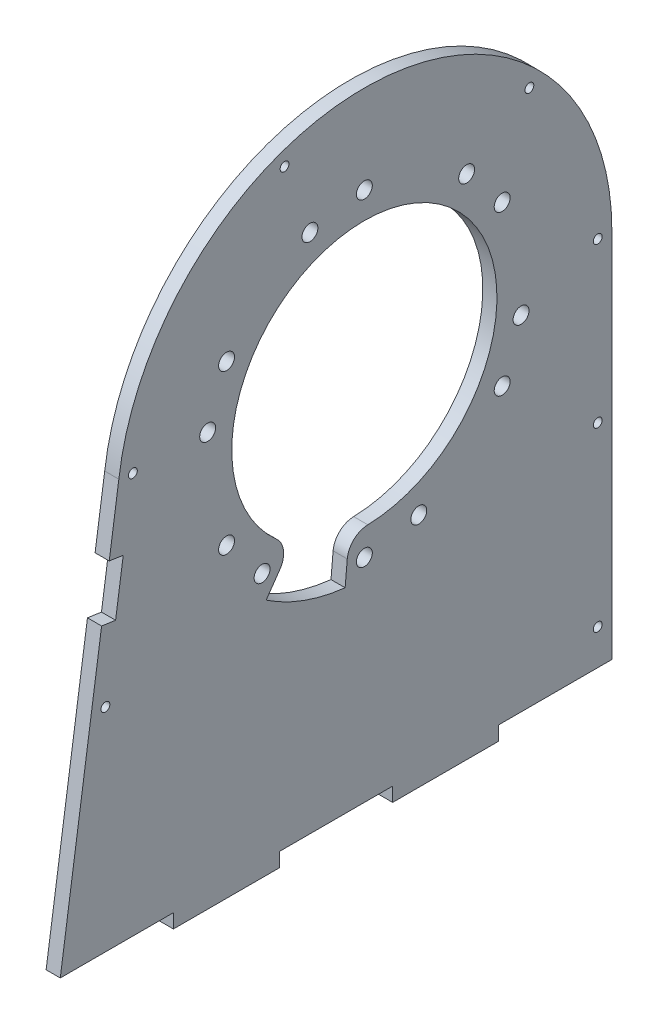
SolidWorks part; units mm, degrees
ref_plane "Ebene vorne" through (0, 0, 0) normal (1, 0, 0) x (0, 1, 0)
ref_plane "Ebene oben" through (0, 0, 0) normal (0, 0, 1) x (0, 1, 0)
ref_plane "Ebene rechts" through (0, 0, 0) normal (0, 1, 0) x (-1, 0, 0)
sketch "Skizze1" plane through (0, 0, 0) normal (1, 0, 0) x (0, 0, -1)
  line L0 (-80.9035, -101.1719) -> (-80.9035, -97.0207)
  line L1 (-121.1235, -18.7355) -> (-120.9035, -18.7355) construction
  line L2 (-96.4035, -81.5207) -> (-102.1906, -81.5207)
  line L3 (-80.9035, -63.7029) -> (-80.9035, -66.0207)
  line L4 (-80.9035, -101.1719) -> (-80.9035, -97.0207)
  line L5 (-61.4088, -81.5207) -> (-65.4035, -81.5207)
  line L6 (-80.9035, -66.0207) -> (-80.9035, -63.7029)
  line L7 (-120.9035, -13.3959) -> (-120.9035, -24.0751)
  line L39 (-10.9035, -186.5207) -> (-166.9035, -186.5207)
  line L40 (-166.9035, -186.5207) -> (-150.3378, -72.6399)
  line L41 (-61.4088, -81.5207) -> (-65.4035, -81.5207)
  line L42 (-10.9035, -81.5207) -> (-10.9035, -186.5207)
  line L43 (-166.9035, -186.5207) -> (-121.9035, -186.5207)
  line L47 (-10.9035, -186.5207) -> (-81.9035, -186.5207)
  line L52 (-1.9035, -186.5207) -> (-10.9035, -186.5207)
  line L54 (-1.9035, -81.5207) -> (-1.9035, -186.5207)
  circle A1 centre (-80.9035, -81.5207) radius 10
  circle A2 centre (-80.9035, -81.5207) radius 15.5
  arc A3 (-38.3408, -137.0943) -> (-38.2029, -136.9884) centre (-80.9035, -81.5207) ccw
  arc A4 (-112.4679, -144.0002) -> (-112.3746, -144.0473) centre (-80.9035, -81.5207) ccw
  arc A6 (-10.9035, -81.5207) -> (-150.3378, -72.6399) centre (-80.9035, -81.5207) ccw
  arc A9 (-38.3408, -137.0943) -> (-38.2029, -136.9884) centre (-80.9035, -81.5207) ccw
  arc A10 (-120.9035, -24.0751) -> (-150.3378, -72.6399) centre (-80.9035, -81.5207) ccw
  arc A11 (-112.4679, -144.0002) -> (-112.3746, -144.0473) centre (-80.9035, -81.5207) ccw
  circle A12 centre (-27.828, -81.5207) radius 3
  circle A13 centre (-44.9035, -120.5207) radius 3
  circle A14 centre (-44.9035, -42.5207) radius 3
  circle A15 centre (-116.9035, -42.5207) radius 3
  circle A16 centre (-116.9035, -120.5207) radius 3
  arc A18 (-1.9035, -81.5207) -> (-120.9035, -13.3959) centre (-80.9035, -81.5207) ccw
  circle A19 centre (-133.9789, -81.5207) radius 3
  circle A20 centre (-80.9035, -28.4453) radius 3
  circle A21 centre (-80.9035, -134.5962) radius 3
  circle A23 centre (-80.9035, -46.5207) radius 1
  circle A24 centre (-80.9035, -116.5207) radius 1
  point P19 (-120.9035, -18.7355)
  point P91 (-121.1235, -18.7355)
  dimension "D1" = 70
  dimension "D2" = 156
extrude "Aufsatz-Linear austragen1" add sketch "Skizze1" along normal blind 4 contours L39 L40 A10 L7 A18 L54 L52
extrude "Schnitt-Linear austragen1" cut sketch "Skizze1<9>" along normal blind 6 contours A1
sketch "Skizze1<9>" plane through (0, 0, 0) normal (1, 0, 0) x (0, 0, -1) same geometry as "Skizze1"
hole_wizard "Ø4.1 (4.1) Durchmesser Bohrung1" positions "Skizze2" profile "Skizze3" hole size "Ø4.1" standard "DIN"
sketch "Skizze2" plane through (0, 0, 0) normal (-1, 0, 0) x (0, 0, 1)
  point P0 (80.9035, -66.0207)
  point P3 (96.4035, -81.5207)
  point P6 (80.9035, -97.0207)
  point P9 (65.4035, -81.5207)
sketch "Skizze3" plane through (0, -66.0207, 80.9035) normal (0, 1, 0) x (0, 0, 1)
  line L0 (0, 0) -> (0, 21.2318)
  line L1 (0, 21.2318) -> (2.05, 20)
  line L2 (2.05, 20) -> (2.05, 0)
  line L5 (2.05, 0) -> (0, 0)
  line L10 (0, 21.2318) -> (-2.05, 20) construction
  line L11 (0, -6.35) -> (0, 107.95) construction
  dimension "Bohrerdurchmesser" = 4.1
  dimension "Bohrungstiefe" = 20
  dimension "Spitzenwinkel" = 118
chamfer "Fase1" distance 1 angle 45 8 edges at (0, -97.0207, 82.9535) (4, -97.0207, 78.8535) (0, -81.5207, 67.4535) (4, -81.5207, 63.3535) (0, -66.0207, 82.9535) (4, -66.0207, 78.8535) (0, -81.5207, 98.4535) (4, -81.5207, 94.3535)
sketch "Skizze4" plane through (0, 0, 0) normal (1, 0, 0) x (0, 0, -1)
  line L0 (-10.9035, -81.5207) -> (-151.4737, -81.5207)
  line L1 (-146.9035, -81.5207) -> (-159.5903, -180.7127)
  line L2 (-80.9035, -11.5207) -> (-80.9035, -186.5207)
  line L3 (-14.9035, -81.5207) -> (-14.9035, -131.5207)
  line L4 (-80.9035, -11.5207) -> (-80.9035, -81.5207)
  line L5 (-102.9035, -81.5207) -> (-113.4035, -81.5207)
  line L6 (-80.9035, -59.5207) -> (-80.9035, -49.0207)
  line L7 (-58.9035, -81.5207) -> (-48.4035, -81.5207)
  line L8 (-80.9035, -103.5207) -> (-80.9035, -114.0207)
  line L9 (-80.9035, -11.5207) -> (-80.9035, -15.5207)
  line L10 (-10.9035, -81.5207) -> (-14.9035, -81.5207)
  line L11 (-151.4737, -81.5207) -> (-146.9035, -81.5207)
  line L12 (-14.9035, -131.5207) -> (-14.9035, -181.5207)
  line L14 (-80.9035, -81.5207) -> (-129.4035, -81.5207)
  line L15 (-25.9035, -171.5208) -> (-55.9035, -171.5208)
  line L16 (-131.2851, -110.731) -> (-126.3188, -110.731)
  line L17 (-35.9035, -118.0036) -> (-42.9648, -118.0036)
  line L18 (-95.9035, -145.7936) -> (-95.9035, -136.0643)
  line L19 (-65.9035, -145.7936) -> (-65.9035, -136.0643)
  line L20 (-147.8627, -186.5207) -> (-147.8627, -171.5208)
  line L21 (-80.9035, -81.5207) -> (-80.9035, -36.7507)
  line L24 (-141.2043, -119.4623) -> (-147.8627, -171.5208)
  line L25 (-147.8627, -171.5208) -> (-135.9031, -171.5208)
  line L26 (-80.9035, -81.5207) -> (-32.4035, -81.5207)
  line L27 (-25.9035, -128.0036) -> (-25.9035, -171.5208)
  line L29 (-80.9035, -181.5207) -> (-80.9035, -139.7707)
  line L31 (-65.9035, -161.5208) -> (-65.9035, -145.7936)
  line L33 (-80.9035, -181.5207) -> (-80.9035, -136.3407)
  line L35 (-95.9035, -161.5208) -> (-95.9035, -145.7936)
  line L36 (-105.9035, -171.5208) -> (-135.9031, -171.5208)
  line L37 (-80.9035, -81.5207) -> (-80.9035, -36.7507)
  line L40 (-80.9035, -81.5207) -> (-36.1335, -81.5207)
  line L41 (-80.9035, -81.5207) -> (-80.9035, -33.0207)
  line L44 (-80.9035, -81.5207) -> (-125.6735, -81.5207)
  line L45 (-80.9035, -81.5207) -> (-80.9035, -33.0207)
  circle A1 centre (-80.9035, -81.5207) radius 22
  circle A2 centre (-80.9035, -81.5207) radius 27
  circle A4 centre (-146.9035, -81.5207) radius 1.2501
  circle A5 centre (-14.9035, -81.5207) radius 1.2501
  circle A6 centre (-80.9035, -15.5207) radius 1.25
  circle A7 centre (-48.4035, -81.5207) radius 1.65
  arc A10 (-14.9107, -82.7708) -> (-146.8962, -82.7708) centre (-80.9035, -81.5207) ccw
  arc A11 (-118.7496, -114.196) -> (-101.7368, -126.9737) centre (-80.9035, -81.5207) ccw
  arc A12 (-60.0701, -126.9737) -> (-49.2879, -120.2565) centre (-80.9035, -81.5207) ccw
  arc A13 (-25.9035, -128.0036) -> (-35.9035, -118.0036) centre (-35.9035, -128.0036) ccw
  arc A14 (-49.2879, -120.2565) -> (-42.9648, -118.0036) centre (-42.9648, -128.0036) cw
  arc A15 (-65.9035, -136.0643) -> (-60.0701, -126.9737) centre (-55.9035, -136.0643) cw
  arc A16 (-95.9035, -136.0643) -> (-101.7368, -126.9737) centre (-105.9035, -136.0643) ccw
  arc A17 (-126.3188, -110.731) -> (-118.7496, -114.196) centre (-126.3188, -120.731) cw
  arc A18 (-141.2043, -119.4623) -> (-131.2851, -110.731) centre (-131.2851, -120.731) cw
  arc A19 (-55.9035, -171.5208) -> (-65.9035, -161.5208) centre (-55.9035, -161.5208) cw
  arc A20 (-105.9035, -171.5208) -> (-95.9035, -161.5208) centre (-105.9035, -161.5208) ccw
  circle A22 centre (-125.6735, -33.0207) radius 1.5
  circle A23 centre (-36.1335, -33.0207) radius 1.5
  point P67 (-65.9035, -129.2177)
  dimension "D3" = 10
  dimension "D4" = 10
extrude "Schnitt-Linear austragen2" cut sketch "Skizze1<18>" against normal blind 10 and the other way through all contours L54 A18 L7 A6 L42 L52 region at (0, -14.8623, 42.7429)
sketch "Skizze1<18>" plane through (0, 0, 0) normal (1, 0, 0) x (0, 0, -1) same geometry as "Skizze1"
hole_wizard "Ø4.8 (4.8) Durchmesser Bohrung1" positions "Skizze17" profile "Skizze18" hole size "Ø4.8" standard "ISO"
sketch "Skizze17" plane through (4, 0, 0) normal (1, 0, 0) x (0, 0, -1)
  point P0 (-80.9035, -46.5207)
  point P3 (-80.9035, -116.5207)
sketch "Skizze18" plane through (4, -46.5207, 80.9035) normal (0, 1, 0) x (0, 0, -1)
  line L0 (0, 0) -> (0, 5.4421)
  line L1 (0, 5.4421) -> (2.4, 4)
  line L2 (2.4, 4) -> (2.4, 0)
  line L5 (2.4, 0) -> (0, 0)
  line L10 (0, 5.4421) -> (-2.4, 4) construction
  line L11 (0, -6.35) -> (0, 107.95) construction
  dimension "Bohrerdurchmesser" = 4.8
  dimension "Bohrungstiefe" = 4
  dimension "Spitzenwinkel" = 118
sketch "Skizze21" plane through (4, 0, 0) normal (1, 0, 0) x (0, 1, 0)
  circle A0 centre (-81.5207, 80.9035) radius 37.5
  dimension "D1" = 75
extrude "Schnitt-Linear austragen3" cut sketch "Skizze21" against normal through all
hole_wizard "Durchgangsloch für M41" positions "Skizze22" profile "Skizze23" hole size "M4" standard "ANSI Metric" end condition through all
sketch "Skizze22" plane through (4, 0, 0) normal (1, 0, 0) x (0, 0, -1)
  line L1 (-80.9035, -81.5207) -> (-80.9035, -126.5207) construction
  line L2 (-65.5125, -123.8069) -> (-80.9035, -81.5207) construction
  circle A0 centre (-80.9035, -81.5207) radius 37.5 construction
  circle A1 centre (-80.9035, -81.5207) radius 37.5 construction
  circle A2 centre (-80.9035, -81.5207) radius 45 construction
  point P0 (-80.9035, -126.5207)
  point P34 (-65.5125, -123.8069)
  dimension "D1" = 90
  dimension "D2" = 20
sketch "Skizze23" plane through (4, -126.5207, 80.9035) normal (0, 1, 0) x (0, 0, -1)
  line L0 (0, 0) -> (0, 4)
  line L1 (0, 4) -> (2.25, 4)
  line L2 (2.25, 4) -> (2.25, 0)
  line L5 (2.25, 0) -> (0, 0)
  line L11 (0, -6.35) -> (0, 107.95) construction
  dimension "Bohrerdurchmesser" = 4.5
  dimension "Bohrungstiefe" = 4
pattern_circular "Kreismuster1" count 6 over 360 about axis through (4, -81.5207, 80.9035) along (1, 0, 0) of "Durchgangsloch für M41"
sketch "Skizze27" plane through (4, 0, 0) normal (1, 0, 0) x (0, 1, 0)
  line L2 (-186.5207, 10.9035) -> (-186.5207, 166.9035) construction
  line L3 (-81.5207, 14.9035) -> (-186.5207, 14.9035)
  line L4 (-81.5207, 14.9035) -> (-186.5207, 14.9035) construction
  line L5 (-34.8517, 34.2344) -> (-81.5207, 80.9035) construction
  line L6 (-81.5207, 80.9035) -> (-81.5207, 14.9035) construction
  line L7 (-81.5207, 80.9035) -> (-19.501, 103.4768) construction
  line L11 (-186.5207, 166.9035) -> (-72.6399, 150.3378) construction
  line L12 (-81.5207, 80.9035) -> (-73.1474, 146.3701) construction
  arc A2 (-81.5207, 14.9035) -> (-73.1474, 146.3701) centre (-81.5207, 80.9035) ccw
  arc A3 (-81.5207, 14.9035) -> (-73.1474, 146.3701) centre (-81.5207, 80.9035) ccw construction
  point P0 (-176.5207, 14.9035)
  point P1 (-126.5207, 14.9035)
  point P4 (-34.8517, 34.2344)
  point P5 (-34.8517, 34.2344)
  point P8 (-19.501, 103.4768)
  point P11 (-81.5207, 14.9035)
  point P12 (-73.1474, 146.3701)
  point P17 (-176.5207, 14.9035)
  point P19 (-126.5207, 14.9035)
  point P41 (-126.5207, 154.1335)
  dimension "D2" = 10
  dimension "D3" = 60
  dimension "D4" = 45
  dimension "D5" = 110
  dimension "D6" = 60
  dimension "D7" = 4
  dimension "D8" = 62.711
  dimension "D1" = 4
hole_wizard "M3 Gewindebohrung1" positions "Skizze27" profile "Skizze28" tap size "M3" standard "DIN"
sketch "Skizze28" plane through (4, -176.5207, 14.9035) normal (0, 1, 0) x (0, 0, -1)
  line L0 (0, 0) -> (0, 9.2511)
  line L1 (0, 9.2511) -> (1.25, 8.5)
  line L2 (1.25, 8.5) -> (1.25, 0)
  line L5 (1.25, 0) -> (0, 0)
  line L10 (0, 9.2511) -> (-1.25, 8.5) construction
  line L11 (0, -6.35) -> (0, 107.95) construction
  dimension "Bohrerdurchmesser" = 2.5
  dimension "Bohrungstiefe" = 8.5
  dimension "Spitzenwinkel" = 118
sketch "Skizze29" plane through (4, 0, 0) normal (1, 0, 0) x (0, 1, 0)
  line L0 (-106.1532, 155.2128) -> (-106.729, 151.2545)
  line L1 (-186.5207, 166.9035) -> (-72.6399, 150.3378) construction
  line L2 (-106.729, 151.2545) -> (-91.8853, 149.0952)
  line L3 (-91.8853, 149.0952) -> (-91.3095, 153.0536)
  line L4 (-106.1532, 155.2128) -> (-91.3095, 153.0536)
  circle A0 centre (-126.5207, 154.1335) radius 1.25 construction
  dimension "D2" = 4
  dimension "D5" = 20
  dimension "D1" = 4
  dimension "D3" = 15
  dimension "D4" = 90
extrude "Schnitt-Linear austragen4" cut sketch "Skizze29" against normal through all contours L2 L3 L4 L0
sketch "Skizze30" plane through (4, 0, 0) normal (1, 0, 0) x (0, 1, 0)
  line L0 (-118.7701, 85.2316) -> (-131.224, 86.3431)
  line L1 (-112.8375, 101.5313) -> (-123.0921, 108.6851)
  arc A0 (-123.0921, 108.6851) -> (-131.224, 86.3431) centre (-81.5207, 80.9035) ccw
  circle A1 centre (-115.9927, 109.8289) radius 2.25 construction
  circle A2 centre (-126.5207, 80.9035) radius 2.25 construction
  circle A3 centre (-81.5207, 80.9035) radius 37.5 construction
  arc A4 (-112.8375, 101.5313) -> (-118.7701, 85.2316) centre (-81.5207, 80.9035) ccw
  dimension "D1" = 100
  dimension "D2" = 5
  dimension "D3" = 5
extrude "Schnitt-Linear austragen5" cut sketch "Skizze30" against normal through all
fillet "Verrundung1" radius 6 2 edges at (2, -118.7701, 85.2316) (2, -112.8375, 101.5313)
sketch "Skizze31" plane through (0, -186.5207, 0) normal (0, -1, 0) x (1, 0, 0)
  line L0 (0, 10.9035) -> (0, 166.9035) construction
  line L1 (0, 42.9035) -> (4, 42.9035)
  line L2 (0, 42.9035) -> (0, 72.9035)
  line L3 (0, 72.9035) -> (4, 72.9035)
  line L4 (4, 42.9035) -> (4, 72.9035)
  line L5 (4, 10.9035) -> (4, 166.9035) construction
  line L6 (4, 10.9035) -> (0, 10.9035) construction
  line L7 (4, 166.9035) -> (0, 166.9035) construction
  line L8 (0, 134.9035) -> (4, 134.9035)
  line L9 (0, 134.9035) -> (0, 104.9035)
  line L10 (0, 104.9035) -> (4, 104.9035)
  line L11 (4, 134.9035) -> (4, 104.9035)
  dimension "D1" = 30
  dimension "D2" = 32
  dimension "D3" = 30
  dimension "D4" = 32
extrude "Aufsatz-Linear austragen2" add sketch "Skizze31" along normal blind 4
equation "\"D3@Skizze31\"=\"D1@Skizze31\""
